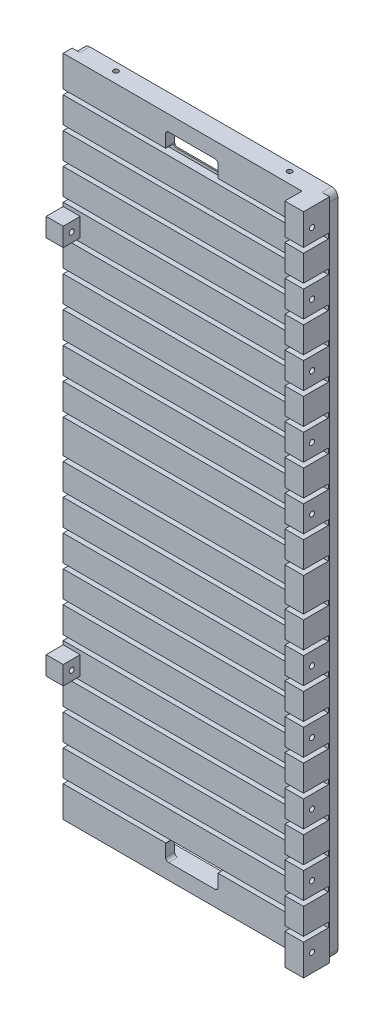
SolidWorks part; units mm, degrees
material "6061-T6 (SS)"
ref_plane "Front Plane" through (0, 0, 0) normal (0, 0, 1) x (1, 0, 0)
ref_plane "Top Plane" through (0, 0, 0) normal (0, 1, 0) x (1, 0, 0)
ref_plane "Right Plane" through (0, 0, 0) normal (1, 0, 0) x (0, 0, -1)
sketch "Sketch1" plane through (0, 0, 0) normal (0, 0, 1) x (1, 0, 0)
  line L1 (-41.5, -107) -> (41.5, -107)
  line L2 (-41.5, -107) -> (-41.5, 107)
  line L3 (-41.5, 107) -> (41.5, 107)
  line L4 (41.5, -107) -> (41.5, 107)
  line L5 (-41.5, -107) -> (41.5, 107) construction
  line L6 (-41.5, 107) -> (41.5, -107) construction
  point P0 (0, 0)
  dimension "D1" = 83
  dimension "D2" = 214
extrude "Boss-Extrude1" add sketch "Sketch1" along normal blind 8.4
sketch "Sketch2" plane through (0, 107, 0) normal (0, 1, 0) x (1, 0, 0)
  line L0 (41.5, -8.4) -> (41.5, 0) construction
  line L1 (-41.5, -8.4) -> (35.5, -8.4)
  line L2 (-41.5, -8.4) -> (-41.5, -2.9)
  line L3 (-41.5, -2.9) -> (35.5, -2.9)
  line L4 (35.5, -8.4) -> (35.5, -2.9)
  dimension "D1" = 5.5
  dimension "D2" = 6
extrude "Cut-Extrude1" cut sketch "Sketch2" against normal through all
sketch "Sketch3" plane through (41.5, 0, 0) normal (1, 0, 0) x (0, 0, -1)
  line L0 (-8.4, -107) -> (-8.4, 107) construction
  line L1 (-8.4, 97) -> (-0.4, 97)
  line L2 (-8.4, 97) -> (-8.4, 95.4)
  line L3 (-8.4, 95.4) -> (-0.4, 95.4)
  line L4 (-0.4, 97) -> (-0.4, 95.4)
  line L5 (-8.4, 107) -> (0, 107) construction
  dimension "D1" = 1.6
  dimension "D2" = 8
  dimension "D3" = 10
extrude "Cut-Extrude2" cut sketch "Sketch3" against normal through all
pattern_linear "LPattern1" count 10 spacing 10 along (0, -1, 0) of "Cut-Extrude2"
mirror "Mirror1" about plane through (0, 0, 0) normal (0, 1, 0) of "LPattern1"
sketch "Sketch4" plane through (0, 0, 0) normal (0, 0, -1) x (-1, 0, 0)
  line L0 (-41.5, 107) -> (41.5, 107) construction
  line L1 (-39, 107) -> (39, 107)
  line L2 (-41, 105) -> (-41, -105)
  line L3 (-39, -107) -> (39, -107)
  line L4 (41, 105) -> (41, -105)
  line L5 (-33.5, -102) -> (33.5, -102)
  line L6 (-35.5, -100) -> (-35.5, 100)
  line L7 (-33.5, 102) -> (33.5, 102)
  line L8 (35.5, -100) -> (35.5, 100)
  line L9 (-35.5, -102) -> (35.5, 102) construction
  line L10 (-35.5, 102) -> (35.5, -102) construction
  line L11 (41.5, -107) -> (-41.5, -107) construction
  arc A0 (-41, -105) -> (-39, -107) centre (-39, -105) ccw
  arc A1 (39, -107) -> (41, -105) centre (39, -105) ccw
  arc A2 (39, 107) -> (41, 105) centre (39, 105) cw
  arc A3 (-39, 107) -> (-41, 105) centre (-39, 105) ccw
  arc A4 (33.5, -102) -> (35.5, -100) centre (33.5, -100) ccw
  arc A5 (-33.5, -102) -> (-35.5, -100) centre (-33.5, -100) cw
  arc A6 (-35.5, 100) -> (-33.5, 102) centre (-33.5, 100) cw
  arc A7 (33.5, 102) -> (35.5, 100) centre (33.5, 100) cw
  point P10 (41.5, -107)
  point P15 (-41.5, 107)
  point P16 (0, 0)
  dimension "D1" = 2
  dimension "D4" = 2
  dimension "D2" = 5
  dimension "D3" = 5.5
  dimension "D5" = 41
  dimension "D6" = 41
extrude "Boss-Extrude2" add sketch "Sketch4" along normal blind 3.18
sketch "Sketch5" plane through (0, 0, 2.9) normal (0, 0, 1) x (1, 0, 0)
  line L0 (-41.5, 57) -> (-41.5, 65.4) construction
  line L1 (-36, 58.2) -> (-41.5, 58.2)
  line L2 (-36, 58.2) -> (-36, 64.2)
  line L3 (-36, 64.2) -> (-41.5, 64.2)
  line L4 (-41.5, 58.2) -> (-41.5, 64.2)
  line L5 (-36, 58.2) -> (-41.5, 64.2) construction
  line L6 (-36, 64.2) -> (-41.5, 58.2) construction
  line L8 (35.5, 65.4) -> (-41.5, 65.4) construction
  point P0 (-38.75, 61.2)
  dimension "D1" = 6
  dimension "D2" = 5.5
  dimension "D3" = 4.2
extrude "Boss-Extrude3" add sketch "Sketch5" along normal blind 5.5
mirror "Mirror2" about plane through (0, 0, 0) normal (0, 1, 0) of "Boss-Extrude3"
sketch "Sketch6" plane through (0, 0, 0) normal (0, 0, -1) x (-1, 0, 0)
  line L0 (33.5, 102) -> (-33.5, 102) construction
  line L1 (-7.475, 96.3) -> (7.475, 96.3)
  line L2 (-8.475, 97.3) -> (-8.475, 101)
  line L3 (-7.475, 102) -> (7.475, 102)
  line L4 (8.475, 97.3) -> (8.475, 101)
  line L5 (-8.475, 96.3) -> (8.475, 102) construction
  line L6 (-8.475, 102) -> (8.475, 96.3) construction
  arc A0 (-8.475, 101) -> (-7.475, 102) centre (-7.475, 101) cw
  arc A1 (7.475, 102) -> (8.475, 101) centre (7.475, 101) cw
  arc A2 (7.475, 96.3) -> (8.475, 97.3) centre (7.475, 97.3) ccw
  arc A3 (-7.475, 96.3) -> (-8.475, 97.3) centre (-7.475, 97.3) cw
  point P0 (0, 99.15)
  dimension "D3" = 1
  dimension "D1" = 5.7
  dimension "D2" = 16.95
extrude "Cut-Extrude3" cut sketch "Sketch6" against normal through all
mirror "Mirror3" about plane through (0, 0, 0) normal (0, 1, 0) of "Cut-Extrude3"
hole_wizard "M2x0.4 Tapped Hole1" positions "Sketch8" profile "Sketch7" tap size "M2x0.4" standard "ANSI Metric" end condition through all
sketch "Sketch8" plane through (41.5, 0, 0) normal (1, 0, 0) x (0, 0, -1)
  line L0 (-8.4, 97) -> (-8.4, 107) construction
  line L1 (-8.4, 107) -> (0, 107) construction
  line L2 (0, 0) -> (-25.7972, 0) construction
  line L3 (0, -107) -> (0, 107) construction
  point P0 (-5.65, 101.2)
  point P16 (-5.65, 81.2)
  point P17 (-5.65, 61.2)
  point P18 (-5.65, 41.2)
  point P19 (-5.65, 21.2)
  point P34 (-5.65, -101.2)
  point P35 (-5.65, -81.2)
  point P36 (-5.65, -61.2)
  point P37 (-5.65, -41.2)
  point P38 (-5.65, -21.2)
  dimension "D1" = 2.75
  dimension "D2" = 5.8
  dimension "D3" = 5
sketch "Sketch7" plane through (41.5, 101.2, 5.65) normal (0, 1, 0) x (0, 0, -1)
  line L0 (0, 0) -> (0, 83)
  line L1 (0, 83) -> (0.8, 83)
  line L2 (0.8, 83) -> (0.8, 0)
  line L5 (0.8, 0) -> (0, 0)
  line L11 (0, -6.35) -> (0, 107.95) construction
  dimension "Thread Major Dia." = 1.6
  dimension "Thru Tap Drill Depth" = 83
hole_wizard "M2x0.4 Tapped Hole2" positions "Sketch10" profile "Sketch11" tap size "M2x0.4" standard "ANSI Metric"
sketch "Sketch10" plane through (0, 0, -3.18) normal (0, 0, -1) x (-1, 0, 0)
  line L0 (39, 107) -> (-39, 107) construction
  line L1 (-41, 105) -> (-41, -105) construction
  line L3 (-35.5, 0) -> (35.5, 0) construction
  line L4 (-35.5, 100) -> (-35.5, -100) construction
  line L5 (35.5, -100) -> (35.5, 100) construction
  point P0 (-37.5, 101.2)
  point P15 (37.5, 101.2)
  point P16 (37.5, 81.2)
  point P17 (37.5, 61.2)
  point P18 (37.5, 41.2)
  point P19 (37.5, 21.2)
  point P20 (-37.5, 81.2)
  point P21 (-37.5, 61.2)
  point P22 (-37.5, 41.2)
  point P23 (-37.5, 21.2)
  point P32 (37.5, -101.2)
  point P33 (-37.5, -21.2)
  point P34 (-37.5, -41.2)
  point P35 (-37.5, -61.2)
  point P36 (-37.5, -81.2)
  point P37 (37.5, -21.2)
  point P38 (37.5, -41.2)
  point P39 (37.5, -61.2)
  point P40 (37.5, -81.2)
  point P41 (-37.5, -101.2)
  dimension "D1" = 5.8
  dimension "D2" = 3.5
  dimension "D5" = 2
  dimension "D3" = 5
sketch "Sketch11" plane through (37.5, 101.2, -3.18) normal (1, 0, 0) x (0, 1, 0)
  line L0 (0, 0) -> (0, 4.4807)
  line L1 (0, 4.4807) -> (0.8, 4)
  line L2 (0.8, 4) -> (0.8, 0)
  line L5 (0.8, 0) -> (0, 0)
  line L10 (0, 4.4807) -> (-0.8, 4) construction
  line L11 (0, -6.35) -> (0, 107.95) construction
  dimension "Tap Drill Dia." = 1.6
  dimension "Tap Drill Depth" = 4
  dimension "Drill Angle" = 118
sketch "Sketch12" plane through (0, 0, 2.9) normal (0, 0, 1) x (1, 0, 0)
  line L1 (28, 71.95) -> (34.5, 71.95)
  line L2 (27, 72.95) -> (27, 79.45)
  line L3 (28, 80.45) -> (34.5, 80.45)
  line L4 (35.5, 72.95) -> (35.5, 79.45)
  line L5 (-35.714, 77) -> (-35.714, 75.4) construction
  line L6 (-41.5, 77) -> (35.5, 77) construction
  line L7 (35.5, 75.4) -> (-41.5, 75.4) construction
  line L8 (41.5, 67) -> (41.5, 75.4) construction
  arc A0 (35.5, 72.95) -> (34.5, 71.95) centre (34.5, 72.95) cw
  arc A1 (34.5, 80.45) -> (35.5, 79.45) centre (34.5, 79.45) cw
  arc A2 (27, 79.45) -> (28, 80.45) centre (28, 79.45) cw
  arc A3 (27, 72.95) -> (28, 71.95) centre (28, 72.95) ccw
  point P6 (27, 76.2)
  point P19 (-35.714, 76.2)
  dimension "D1" = 1
  dimension "D2" = 8.5
  dimension "D3" = 8.5
  dimension "D4" = 6
extrude "wonky_+Y_RBF_hole" [suppressed] cut sketch "Sketch12" against normal blind 10
hole_wizard "M2x0.4 Tapped Hole3" positions "Sketch13" profile "Sketch14" tap size "M2x0.4" standard "ANSI Metric"
sketch "Sketch13" plane through (0, -107, 0) normal (0, -1, 0) x (-1, 0, 0)
  point P0 (-28, 0.6)
sketch "Sketch14" plane through (28, -107, -0.6) normal (1, 0, 0) x (0, 0, -1)
  line L0 (0, 0) -> (0, 3.9807)
  line L1 (0, 3.9807) -> (0.8, 3.5)
  line L2 (0.8, 3.5) -> (0.8, 0)
  line L5 (0.8, 0) -> (0, 0)
  line L10 (0, 3.9807) -> (-0.8, 3.5) construction
  line L11 (0, -6.35) -> (0, 107.95) construction
  dimension "Tap Drill Dia." = 1.6
  dimension "Tap Drill Depth" = 3.5
  dimension "Drill Angle" = 118
cosmetic thread "Hole Thread1" parameters "D1"=3, "D2"=2
mirror "Mirror4" about plane through (0, 0, 0) normal (1, 0, 0) of "M2x0.4 Tapped Hole3"
mirror "Mirror5" about plane through (0, 0, 0) normal (0, 1, 0) of "Mirror4"
